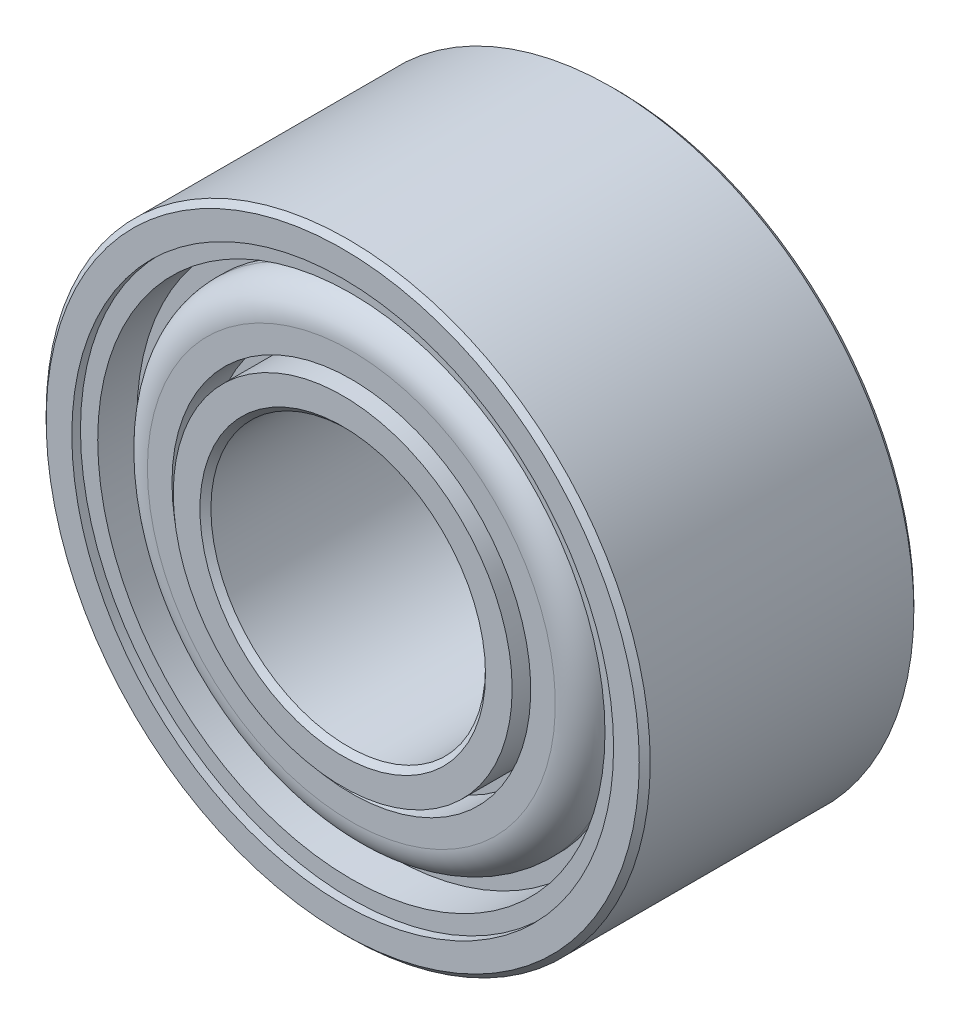
SolidWorks part; units mm, degrees
ref_plane "Front Plane" through (0, 0, 0) normal (0, 0, 1) x (1, 0, 0)
ref_plane "Top Plane" through (0, 0, 0) normal (0, 1, 0) x (1, 0, 0)
ref_plane "Right Plane" through (0, 0, 0) normal (1, 0, 0) x (0, 0, -1)
sketch "Sketch1" plane through (0, 0, 0) normal (1, 0, 0) x (0, 0, -1)
  line L0 (0, 4) -> (0, 0) construction
  line L1 (2.5, 2.5) -> (-2.5, 2.5)
  line L2 (2.5, 2.5) -> (2.5, 5.5)
  line L3 (2.5, 5.5) -> (-2.5, 5.5)
  line L4 (-2.5, 2.5) -> (-2.5, 5.5)
  line L5 (2.5, 2.5) -> (-2.5, 5.5) construction
  line L6 (2.5, 5.5) -> (-2.5, 2.5) construction
  line L7 (0, 0) -> (-6.7364, 0) construction
  point P0 (0, 4)
  point P5 (0, 5.5)
  dimension "D1" = 5
  dimension "D2" = 5.5
  dimension "D3" = 2.5
revolve "Revolve1" add sketch "Sketch1" angle 360 about L7
sketch "Sketch2" plane through (0, 0, 0) normal (1, 0, 0) x (0, 0, -1)
  line L2 (2.3426, 4.9327) -> (2.3426, 4.6184)
  line L3 (2.3426, 4.6184) -> (1.6284, 4.6184)
  line L4 (1.6284, 4.6184) -> (1.6284, 4.3137)
  line L5 (1.6284, 4.3137) -> (2.3426, 4.3137)
  line L6 (2.3426, 4.3137) -> (2.3426, 3.2662)
  line L7 (2.3426, 3.2662) -> (1.6284, 3.2662)
  line L8 (1.6284, 3.2662) -> (1.6284, 3.0853)
  line L9 (1.6284, 3.0853) -> (3.1901, 3.0853)
  line L10 (3.1901, 3.0853) -> (3.1901, 4.9327)
  line L11 (3.1901, 4.9327) -> (2.3426, 4.9327)
  line L12 (0, 0) -> (0, 6.9229) construction
  line L13 (-3.1901, 4.9327) -> (-2.3426, 4.9327)
  line L14 (-3.1901, 3.0853) -> (-3.1901, 4.9327)
  line L15 (-1.6284, 3.0853) -> (-3.1901, 3.0853)
  line L16 (-1.6284, 3.2662) -> (-1.6284, 3.0853)
  line L17 (-2.3426, 3.2662) -> (-1.6284, 3.2662)
  line L18 (-2.3426, 4.3137) -> (-2.3426, 3.2662)
  line L19 (-1.6284, 4.3137) -> (-2.3426, 4.3137)
  line L20 (-1.6284, 4.6184) -> (-1.6284, 4.3137)
  line L21 (-2.3426, 4.6184) -> (-1.6284, 4.6184)
  line L22 (-2.3426, 4.9327) -> (-2.3426, 4.6184)
  line L24 (0, 0) -> (-5.8719, 0) construction
revolve "Cut-Revolve1" cut sketch "Sketch2" angle 360 about L24
fillet "Fillet1" radius 0.6 2 edges at (-4.3137, 0, 2.3426) (-4.3137, 0, -2.3426)
chamfer "Chamfer1" distance 0.1 angle 45 4 edges at (-2.5, 0, 2.5) (-2.5, 0, -2.5) (-5.5, 0, 2.5) (-5.5, 0, -2.5)
sketch "Sketch3" plane through (0, 0, 0) normal (0, 0, 1) x (1, 0, 0)
  point P0 (0, 0)
